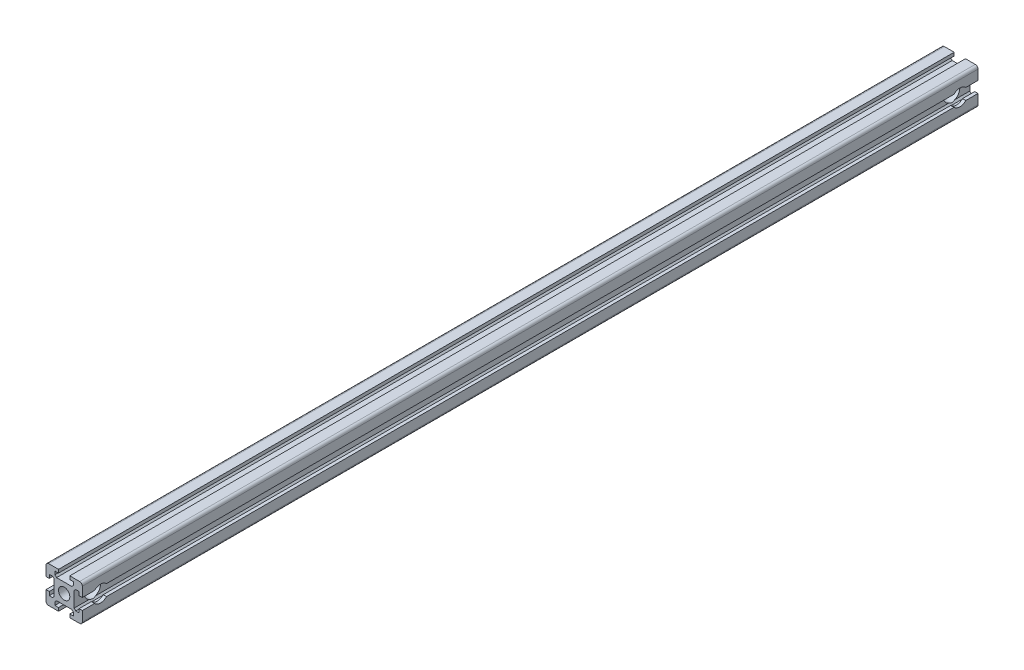
SolidWorks part; units mm, degrees
material "6061 Alloy"
ref_plane "Front Plane" through (0, 0, 0) normal (0, 0, 1) x (1, 0, 0)
ref_plane "Top Plane" through (0, 0, 0) normal (0, 1, 0) x (1, 0, 0)
ref_plane "Right Plane" through (0, 0, 0) normal (1, 0, 0) x (0, 0, -1)
sketch "Sketch1" plane through (0, 0, 0) normal (0, 0, 1) x (1, 0, 0)
  line L0 (-10, 3.1) -> (-8.2, 3.1)
  line L1 (-8.5, 10) -> (-3.1, 10) construction
  line L2 (-10, 8.5) -> (-10, 3.1) construction
  line L3 (-10, -3.1) -> (-10, -8.5) construction
  line L4 (-8.5, -10) -> (-3.1, -10) construction
  line L5 (-10, -3.1) -> (-10, -8.5)
  line L6 (-8.5, -10) -> (-3.1, -10)
  line L7 (-8.2, 3.1) -> (-8.2, 5.1)
  line L8 (-8.2, 5.1) -> (-6.4, 5.1)
  line L9 (-10, -3.1) -> (-8.2, -3.1)
  line L10 (-8.2, -3.1) -> (-8.2, -5.1)
  line L11 (-8.2, -5.1) -> (-6.4, -5.1)
  line L13 (-6.4, 5.1) -> (-5.4929, 4.1929)
  line L14 (-5.4929, 4.1929) -> (-5.4929, -4.1929)
  line L15 (-6.4, -5.1) -> (-5.4929, -4.1929)
  line L16 (-3.1, 10) -> (-3.1, 8.2)
  line L17 (-3.1, 8.2) -> (-5.1, 8.2)
  line L19 (-5.1, 8.2) -> (-5.1, 6.4)
  line L20 (-5.1, 6.4) -> (-4.1929, 5.4929)
  line L21 (-4.1929, 5.4929) -> (4.1929, 5.4929)
  line L22 (4.1929, 5.4929) -> (5.1, 6.4)
  line L23 (5.1, 6.4) -> (5.1, 8.2)
  line L24 (5.1, 8.2) -> (3.1, 8.2)
  line L25 (3.1, 8.2) -> (3.1, 10)
  line L26 (-3.1, -10) -> (-3.1, -8.2)
  line L27 (-3.1, -8.2) -> (-5.1, -8.2)
  line L28 (-5.1, -8.2) -> (-5.1, -6.4)
  line L29 (-5.1, -6.4) -> (-4.1929, -5.4929)
  line L30 (-4.1929, -5.4929) -> (4.1929, -5.4929)
  line L31 (4.1929, -5.4929) -> (5.1, -6.4)
  line L32 (5.1, -6.4) -> (5.1, -8.2)
  line L33 (5.1, -8.2) -> (3.1, -8.2)
  line L34 (3.1, -8.2) -> (3.1, -10)
  line L35 (3.1, -10) -> (8.5, -10)
  line L36 (10, -8.5) -> (10, -3.1)
  line L37 (10, -3.1) -> (8.2, -3.1)
  line L38 (8.2, -3.1) -> (8.2, -5.1)
  line L39 (8.2, -5.1) -> (6.4, -5.1)
  line L40 (6.4, -5.1) -> (5.4929, -4.1929)
  line L41 (5.4929, -4.1929) -> (5.4929, 4.1929)
  line L42 (5.4929, 4.1929) -> (6.4, 5.1)
  line L43 (6.4, 5.1) -> (8.2, 5.1)
  line L44 (8.2, 5.1) -> (8.2, 3.1)
  line L45 (8.2, 3.1) -> (10, 3.1)
  line L46 (10, 3.1) -> (10, 8.5)
  line L47 (8.5, 10) -> (3.1, 10)
  line L48 (-3.1, 10) -> (-8.5, 10)
  line L49 (-10, 8.5) -> (-10, 3.1)
  arc A0 (-8.5, 10) -> (-10, 8.5) centre (-8.5, 8.5) ccw
  arc A1 (-10, -8.5) -> (-8.5, -10) centre (-8.5, -8.5) ccw construction
  arc A2 (8.5, -10) -> (10, -8.5) centre (8.5, -8.5) ccw
  arc A3 (8.5, 10) -> (10, 8.5) centre (8.5, 8.5) cw
  arc A4 (-8.5, -10) -> (-10, -8.5) centre (-8.5, -8.5) cw
  circle A6 centre (0, 0) radius 3.1
  point P0 (0, 0)
  point P44 (-5.2, -3.4858)
  point P47 (-5.2, 3.4858)
  dimension "D3" = 5.4929
  dimension "D5" = 1.5
  dimension "D1" = 6.2
  dimension "D2" = 5.4929
  dimension "D4" = 1.5
  dimension "D6" = 1.5
extrude "Boss-Extrude1" add sketch "Sketch1" along normal blind 493
sketch "Sketch3" plane through (5.4929, 0, 0) normal (1, 0, 0) x (0, 0, -1)
  line L0 (0, -4.1929) -> (0, 4.1929) construction
  line L1 (-493, -10) -> (0, -10) construction
  line L2 (-493, -4.1929) -> (-493, 4.1929) construction
  circle A0 centre (-10, 0) radius 4.5
  circle A1 centre (-483, 0) radius 4.5
  point P4 (0, 0)
  dimension "D1" = 10
  dimension "D2" = 10
  dimension "D3" = 10
  dimension "D4" = 9
extrude "Cut-Extrude2" cut sketch "Sketch3" against normal blind 11 and the other way through all
